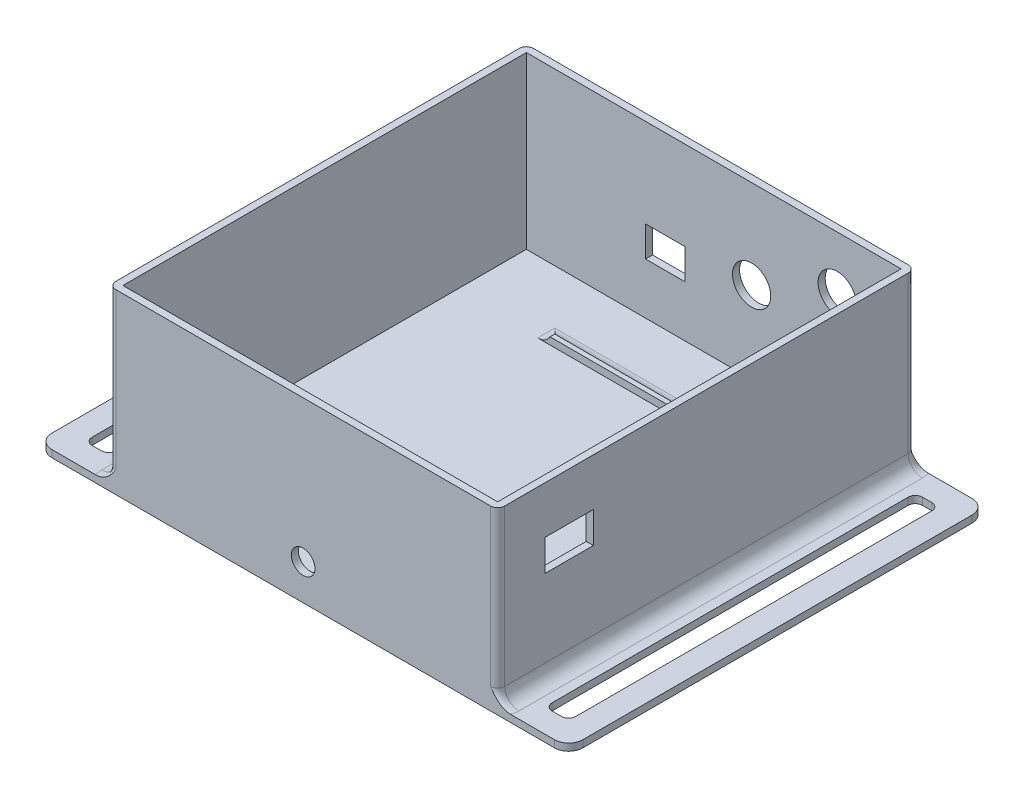
SolidWorks part; units mm, degrees
ref_plane "Front Plane" through (0, 0, 0) normal (0, 0, 1) x (1, 0, 0)
ref_plane "Top Plane" through (0, 0, 0) normal (0, 1, 0) x (1, 0, 0)
ref_plane "Right Plane" through (0, 0, 0) normal (1, 0, 0) x (0, 0, -1)
sketch "Sketch1" plane through (0, 0, 0) normal (0, 1, 0) x (1, 0, 0)
  line L5 (48.0955, 50.4755) -> (48.0955, -59.9645) construction
  line L6 (-70.2045, 80.4755) -> (88.0955, 80.4755)
  line L7 (-29.9045, 50.1755) -> (47.7955, 50.1755) construction
  line L8 (-29.9045, 50.1755) -> (-29.9045, -59.6645) construction
  line L9 (-29.9045, -59.6645) -> (47.7955, -59.6645) construction
  line L10 (47.7955, 50.1755) -> (47.7955, -59.6645) construction
  line L14 (-70.2045, 80.4755) -> (-70.2045, -89.9645)
  line L15 (-70.2045, -89.9645) -> (88.0955, -89.9645)
  line L16 (88.0955, 80.4755) -> (88.0955, -89.9645)
  line L17 (-30.2045, -59.9645) -> (48.0955, -59.9645) construction
  line L18 (-30.2045, 50.4755) -> (-30.2045, -59.9645) construction
  line L19 (-30.2045, 50.4755) -> (48.0955, 50.4755) construction
  line L20 (-30.2045, -59.9645) -> (-70.2045, -59.9645) construction
  line L21 (48.0955, -59.9645) -> (88.0955, -59.9645) construction
  line L22 (-30.2045, 50.4755) -> (-30.2045, 80.4755) construction
  line L23 (-30.2045, -59.9645) -> (-30.2045, -89.9645) construction
  line L24 (-73.2045, 83.4755) -> (-73.2045, -92.9645)
  line L25 (-73.2045, -92.9645) -> (91.0955, -92.9645)
  line L26 (91.0955, 83.4755) -> (91.0955, -92.9645)
  line L27 (-73.2045, 83.4755) -> (91.0955, 83.4755)
  point P0 (0, 0)
  dimension "D1" = 77.7
  dimension "D2" = 109.84
  dimension "D3" = 0.3
  dimension "D4" = 40
  dimension "D5" = 30
  dimension "D6" = 3
extrude "Boss-Extrude1" add sketch "Sketch1" along normal blind 72
sketch "Sketch2" plane through (0, 0, 0) normal (0, -1, 0) x (1, 0, 0)
  line L8 (-73.2045, -83.4755) -> (91.0955, -83.4755)
  line L9 (91.0955, -83.4755) -> (91.0955, 92.9645)
  line L10 (91.0955, 92.9645) -> (-73.2045, 92.9645)
  line L11 (-73.2045, 92.9645) -> (-73.2045, -83.4755)
  line L12 (-73.2045, -83.4755) -> (91.0955, -83.4755)
  line L13 (91.0955, -83.4755) -> (91.0955, 92.9645)
  line L14 (91.0955, 92.9645) -> (-73.2045, 92.9645)
  line L15 (-73.2045, 92.9645) -> (-73.2045, -83.4755)
  dimension "D1" = 0
extrude "Boss-Extrude2" add sketch "Sketch2" along normal blind 3
sketch "Sketch3" plane through (0, 0, -83.4755) normal (0, 0, -1) x (-1, 0, 0)
  line L0 (3.1445, 34.5) -> (3.1445, 21.64)
  line L1 (3.4445, 34.2) -> (19.5645, 34.2) construction
  line L2 (3.4445, 34.2) -> (3.4445, 21.94) construction
  line L3 (3.4445, 21.94) -> (19.5645, 21.94) construction
  line L4 (19.5645, 34.2) -> (19.5645, 21.94) construction
  line L5 (3.1445, 21.64) -> (19.8645, 21.64)
  line L6 (19.8645, 34.5) -> (19.8645, 21.64)
  line L7 (3.1445, 34.5) -> (19.8645, 34.5)
  line L8 (-61.0955, 49.5) -> (-61.0955, 19.5) construction
  line L9 (-91.0955, 34.5) -> (73.2045, 34.5) construction
  line L10 (-91.0955, 72) -> (-91.0955, -3) construction
  line L11 (73.2045, 72) -> (73.2045, -3) construction
  line L12 (-16.8555, 34.5) -> (-24.9355, 42.58) construction
  line L13 (-53.0155, 49.5) -> (-61.0955, 49.5) construction
  line L14 (-33.0155, 34.5) -> (-24.9355, 42.58) construction
  circle A0 centre (-61.0955, 49.5) radius 7.78 construction
  circle A1 centre (-61.0955, 49.5) radius 8.08
  circle A2 centre (-61.0955, 19.5) radius 8.08
  circle A3 centre (-24.9355, 34.5) radius 8.08
  point P22 (-61.0955, 34.5)
  point P24 (11.5045, 34.5)
  dimension "D1" = 15.56
  dimension "D3" = 12.26
  dimension "D4" = 16.12
  dimension "D6" = 30
  dimension "D7" = 30
  dimension "D8" = 20
  dimension "D9" = 20
  dimension "D2" = 0.3
  dimension "D5" = 0.3
extrude "Cut-Extrude1" cut sketch "Sketch3" against normal up to surface (3 mm away) up to face at (8.9455, 36, -80.4755)
sketch "Sketch4" plane through (91.0955, 0, 0) normal (1, 0, 0) x (0, 0, -1)
  line L0 (-72.9645, 52) -> (-72.9645, 38.82)
  line L1 (-72.6645, 51.7) -> (-52.8445, 51.7) construction
  line L2 (-72.6645, 51.7) -> (-72.6645, 39.12) construction
  line L3 (-72.6645, 39.12) -> (-52.8445, 39.12) construction
  line L4 (-52.8445, 51.7) -> (-52.8445, 39.12) construction
  line L5 (-72.9645, 38.82) -> (-52.5445, 38.82)
  line L6 (-52.5445, 52) -> (-52.5445, 38.82)
  line L7 (-72.9645, 52) -> (-52.5445, 52)
  line L8 (-72.9645, 52) -> (-72.9645, 72) construction
  line L9 (-92.9645, 72) -> (83.4755, 72) construction
  line L10 (-72.9645, 52) -> (-92.9645, 52) construction
  line L11 (-92.9645, 72) -> (-92.9645, -3) construction
  dimension "D1" = 12.58
  dimension "D2" = 19.82
  dimension "D4" = 20
  dimension "D3" = 0.3
extrude "Cut-Extrude2" cut sketch "Sketch4" against normal up to surface (3 mm away) up to face at (88.0955, 36, 4.7445)
sketch "Sketch5" plane through (0, 0, 92.9645) normal (0, 0, 1) x (1, 0, 0)
  line L0 (8.9455, 72) -> (8.9455, -3) construction
  line L1 (-73.2045, 72) -> (91.0955, 72) construction
  line L2 (91.0955, -3) -> (-73.2045, -3) construction
  circle A0 centre (8.9455, 12) radius 5
  dimension "D1" = 10
  dimension "D2" = 15
extrude "Cut-Extrude3" cut sketch "Sketch5" against normal up to surface (3 mm away) up to face at (8.9455, 36, 89.9645)
sketch "Sketch6" plane through (-73.2045, 0, 0) normal (-1, 0, 0) x (0, 0, 1)
  line L0 (92.9645, 72) -> (92.9645, -3) construction
  line L1 (-83.4755, -3) -> (92.9645, -3)
  line L2 (-83.4755, -3) -> (-83.4755, 0)
  line L3 (-83.4755, 0) -> (92.9645, 0)
  line L4 (92.9645, -3) -> (92.9645, 0)
  dimension "D1" = 3
extrude "Boss-Extrude3" add sketch "Sketch6" along normal blind 30
sketch "Sketch7" plane through (91.0955, 0, 0) normal (1, 0, 0) x (0, 0, -1)
  line L0 (83.4755, 72) -> (83.4755, -3) construction
  line L1 (-92.9645, -3) -> (83.4755, -3)
  line L2 (-92.9645, -3) -> (-92.9645, 0)
  line L3 (-92.9645, 0) -> (83.4755, 0)
  line L4 (83.4755, -3) -> (83.4755, 0)
  dimension "D1" = 3
extrude "Boss-Extrude4" add sketch "Sketch7" along normal blind 30
sketch "Sketch9" plane through (0, 0, 0) normal (0, 1, 0) x (1, 0, 0)
  line L8 (-83.2045, -82.9645) -> (-83.2045, 73.4755)
  line L9 (-83.2045, 73.4755) -> (-93.2045, 73.4755)
  line L10 (-93.2045, 73.4755) -> (-93.2045, -82.9645)
  line L11 (-93.2045, -82.9645) -> (-83.2045, -82.9645)
  line L12 (-83.2045, -82.9645) -> (-83.2045, 73.4755)
  line L13 (-83.2045, 73.4755) -> (-93.2045, 73.4755)
  line L14 (-93.2045, 73.4755) -> (-93.2045, -82.9645)
  line L15 (-93.2045, -82.9645) -> (-83.2045, -82.9645)
  dimension "D1" = 10
extrude "Cut-Extrude4" cut sketch "Sketch9" against normal through all
sketch "Sketch10" plane through (0, 0, 0) normal (0, 1, 0) x (1, 0, 0)
  line L8 (101.0955, 73.4755) -> (101.0955, -82.9645)
  line L9 (101.0955, -82.9645) -> (111.0955, -82.9645)
  line L10 (111.0955, -82.9645) -> (111.0955, 73.4755)
  line L11 (111.0955, 73.4755) -> (101.0955, 73.4755)
  line L12 (101.0955, 73.4755) -> (101.0955, -82.9645)
  line L13 (101.0955, -82.9645) -> (111.0955, -82.9645)
  line L14 (111.0955, -82.9645) -> (111.0955, 73.4755)
  line L15 (111.0955, 73.4755) -> (101.0955, 73.4755)
  dimension "D1" = 10
extrude "Cut-Extrude5" cut sketch "Sketch10" against normal through all
fillet "Fillet1" radius 3 12 edges at (111.0955, -1.5, 82.9645) (101.0955, -1.5, 82.9645) (111.0955, -1.5, -73.4755) (101.0955, -1.5, -73.4755) (-93.2045, -1.5, 82.9645) (-83.2045, -1.5, 82.9645) (-93.2045, -1.5, -73.4755) (-83.2045, -1.5, -73.4755) (-73.2045, 36, 92.9645) (91.0955, 36, 92.9645) (91.0955, 36, -83.4755) (-73.2045, 36, -83.4755)
fillet "Fillet2" radius 6 10 edges at (90.2168, 0, -82.5968) (90.2168, 0, 92.0859) (-72.3259, 0, 92.0859) (-72.3259, 0, -82.5968) (91.0955, 0, 4.7445) (-73.2045, 0, 4.7445) (-103.2045, -1.5, 92.9645) (121.0955, -1.5, 92.9645) (121.0955, -1.5, -83.4755) (-103.2045, -1.5, -83.4755)
sketch "Sketch11" plane through (0, 0, 0) normal (0, 1, 0) x (1, 0, 0)
  line L0 (-30.2045, 50.4755) -> (-70.2045, 50.4755) construction
  line L1 (-30.2045, 50.4755) -> (48.0955, 50.4755)
  line L2 (-30.2045, 50.4755) -> (-30.2045, -59.9645) construction
  line L3 (-30.2045, -59.9645) -> (48.0955, -59.9645)
  line L4 (48.0955, 50.4755) -> (48.0955, -59.9645) construction
  line L5 (-70.2045, 80.4755) -> (-70.2045, -89.9645) construction
  line L6 (48.0955, 50.4755) -> (88.0955, 50.4755) construction
  line L7 (88.0955, -89.9645) -> (88.0955, 80.4755) construction
  line L8 (48.0955, 50.4755) -> (48.0955, 80.4755) construction
  line L9 (88.0955, 80.4755) -> (-70.2045, 80.4755) construction
  line L10 (48.0955, -59.9645) -> (48.0955, -89.9645) construction
  line L11 (-70.2045, -89.9645) -> (88.0955, -89.9645) construction
  line L13 (-30.2045, 50.4755) -> (48.0955, 50.4755)
  line L14 (-30.2045, 50.4755) -> (-30.2045, 52.4755)
  line L15 (-30.2045, 52.4755) -> (48.0955, 52.4755)
  line L16 (48.0955, 50.4755) -> (48.0955, 52.4755)
  line L17 (48.0955, -59.9645) -> (-30.2045, -59.9645)
  line L18 (48.0955, -59.9645) -> (48.0955, -61.9645)
  line L19 (48.0955, -61.9645) -> (-30.2045, -61.9645)
  line L20 (-30.2045, -59.9645) -> (-30.2045, -61.9645)
  dimension "D1" = 40
  dimension "D2" = 30
  dimension "D3" = 2
extrude "Boss-Extrude5" add sketch "Sketch11" along normal blind 3 contours L1 L16 L15 L14 | L3 L20 L19 L18 region at (8.9455, 0, -51.4755) region at (8.9455, 0, 60.9645)
fillet "Fillet3" radius 6 6 edges at (8.9455, 0, 61.9645) (8.9455, 0, -52.4755) (-30.2045, 0, 60.9645) (48.0955, 0, 60.9645) (48.0955, 0, -51.4755) (-30.2045, 0, -51.4755)
